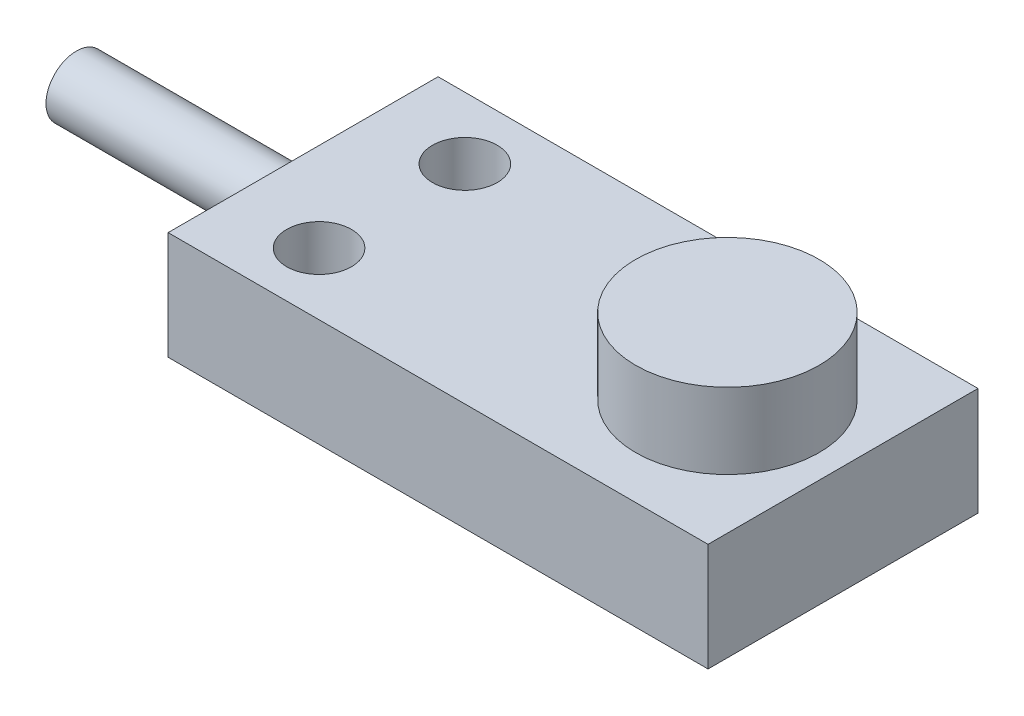
SolidWorks part; units mm, degrees
ref_plane "前视基准面" through (0, 0, 0) normal (0, 0, 1) x (1, 0, 0)
ref_plane "上视基准面" through (0, 0, 0) normal (0, 1, 0) x (1, 0, 0)
ref_plane "右视基准面" through (0, 0, 0) normal (1, 0, 0) x (0, 0, -1)
other "Configuration Table"
sketch "草图1" plane through (0, 0, 0) normal (0, 1, 0) x (1, 0, 0)
  line L0 (0, 0) -> (50000, 0) construction
  line L1 (-25, 12.5) -> (25, 12.5)
  line L2 (-25, 12.5) -> (-25, -12.5)
  line L3 (-25, -12.5) -> (25, -12.5)
  line L4 (25, 12.5) -> (25, -12.5)
  line L5 (-25, 12.5) -> (25, -12.5) construction
  line L6 (-25, -12.5) -> (25, 12.5) construction
  line L7 (0, 0) -> (0, -50000) construction
  circle A0 centre (-16.7698, 6.75) radius 3
  circle A1 centre (-16.7698, -6.75) radius 3
  circle A2 centre (14.2946, 0) radius 8.5
  point P0 (0, 0)
  dimension "D4" = 6
  dimension "D5" = 17
  dimension "D1" = 50
  dimension "D2" = 25
  dimension "D3" = 13.5
extrude "凸台-拉伸1" add sketch "草图1" along normal blind 10 contours L4 L1 L2 L3 A2 A0 A1 | A2 region at (-2.3759, 0, 0) region at (14.2946, 0, 0)
sketch "草图2" plane through (-25, 0, 0) normal (-1, 0, 0) x (0, 0, 1)
  circle A0 centre (0, 5) radius 2.8088
extrude "凸台-拉伸2" add sketch "草图2" along normal blind 21
extrude "凸台-拉伸3" add sketch "草图1<3>" along normal blind 17 contours A2 region at (14.2946, 0, 0)
sketch "草图1<3>" plane through (0, 0, 0) normal (0, 1, 0) x (1, 0, 0) same geometry as "草图1"
